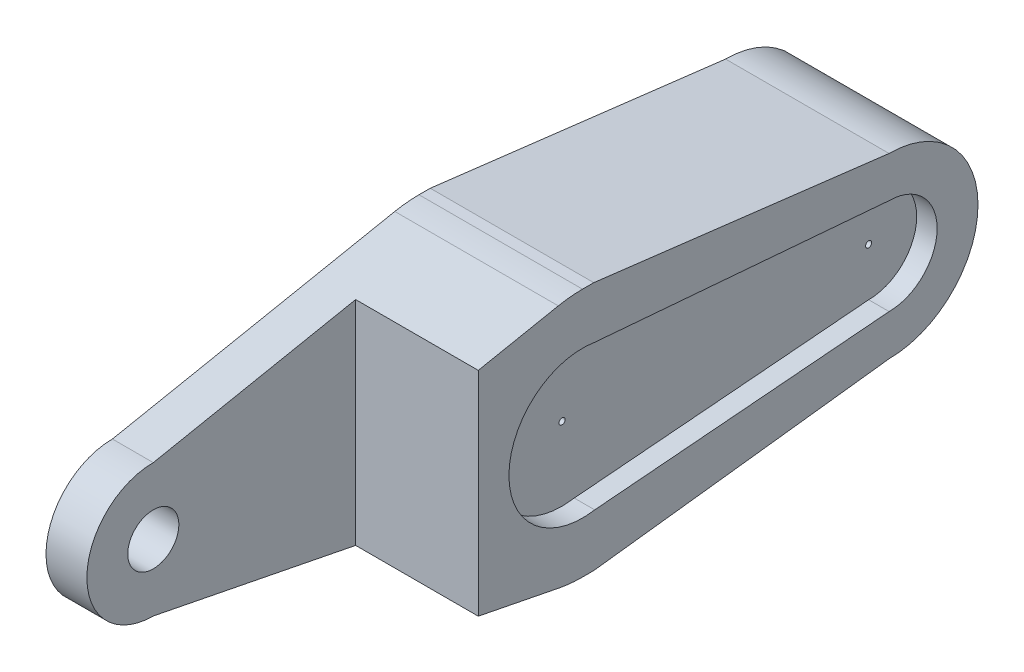
SolidWorks part; units mm, degrees
material "PLA"
ref_plane "Front Plane" through (0, 0, 0) normal (1, 0, 0) x (0, 1, 0)
ref_plane "Top Plane" through (0, 0, 0) normal (0, 0, 1) x (0, 1, 0)
ref_plane "Right Plane" through (0, 0, 0) normal (0, 1, 0) x (-1, 0, 0)
sketch "Sketch2" plane through (0, 0, 0) normal (1, 0, 0) x (0, 1, 0)
  line L0 (0, -13.9832) -> (0, -33.5576) construction
  line L1 (-6.1, -18.8) -> (6.1, -18.8)
  line L2 (-6.1, -18.8) -> (-6.1, 18.8)
  line L3 (-6.1, 18.8) -> (6.1, 18.8)
  line L4 (6.1, -18.8) -> (6.1, 18.8)
  line L5 (-6.1, -18.8) -> (6.1, 18.8) construction
  line L6 (-6.1, 18.8) -> (6.1, -18.8) construction
  line L7 (2.35, -14.45) -> (3.6, 0.55)
  line L8 (-3.6, 0.55) -> (-2.35, -14.45)
  line L9 (-6.1, 0) -> (-4.35, -14.45)
  line L10 (4.35, -14.45) -> (6.1, 0)
  line L11 (-3.25, 15.55) -> (-5.984, 1.7341)
  line L12 (5.984, 1.7341) -> (3.25, 15.55)
  arc A1 (3.5503, -0.0459) -> (-3.5503, -0.0459) centre (0, 0.55) ccw
  arc A2 (-2.35, -14.45) -> (2.35, -14.45) centre (0, -14.45) ccw
  circle A3 centre (0, 15.55) radius 1.25
  arc A4 (3.25, 15.55) -> (-3.25, 15.55) centre (0, 15.55) ccw
  arc A5 (-4.35, -14.45) -> (4.35, -14.45) centre (0, -14.45) ccw
  arc A6 (-5.984, 1.7341) -> (-6.1, 0.55) centre (0, 0.55) ccw
  arc A7 (6.1, 0.55) -> (5.984, 1.7341) centre (0, 0.55) ccw
  point P0 (0, 0)
  point P13 (6.1, -18.8)
  dimension "D1" = 7.2
  dimension "D2" = 4.7
  dimension "D4" = 2.5
  dimension "D5" = 2
  dimension "D8" = 2
  dimension "D3" = 15
  dimension "D6" = 15
  dimension "D7" = 2.5
extrude "Boss-Extrude1" add sketch "Sketch2" along normal blind 8 contours L4 A7 L12 A4 L11 A6 L2 L9 A5 L10 A3 A2 L8 A1 L7 region at (0, -2.7964, -17.2464)
extrude "Boss-Extrude2" add sketch "Sketch2<3>" along normal blind 7 contours L8 A2 L7 A1 region at (0, 0, -5.6231)
sketch "Sketch2<3>" plane through (0, 0, 0) normal (1, 0, 0) x (0, 1, 0) same geometry as "Sketch2"
sketch "Sketch3" plane through (7, 0, 0) normal (1, 0, 0) x (0, 1, 0)
  circle A0 centre (0, 0.55) radius 0.15
  arc A1 (3.6, 0.55) -> (-3.6, 0.55) centre (0, 0.55) ccw construction
  circle A2 centre (0, -14.45) radius 0.15
  arc A3 (-2.35, -14.45) -> (2.35, -14.45) centre (0, -14.45) ccw construction
  dimension "D1" = 0.3
extrude "Cut-Extrude1" cut sketch "Sketch3" against normal through all
sketch "Sketch4" plane through (8, 0, 0) normal (1, 0, 0) x (0, 1, 0)
  line L0 (5.2091, 5.65) -> (-5.2091, 5.65)
  line L1 (5.984, 1.7341) -> (3.25, 15.55) construction
  line L2 (-3.25, 15.55) -> (-5.984, 1.7341) construction
  line L3 (0, 4.15) -> (-5.8706, 4.15) construction
  line L10 (6.1, 0) -> (6.1, 0.55)
  line L11 (5.984, 1.7341) -> (3.25, 15.55)
  line L12 (-3.25, 15.55) -> (-5.984, 1.7341)
  line L13 (-6.1, 0.55) -> (-6.1, 0)
  line L14 (-6.1, 0) -> (-4.35, -14.45)
  line L15 (4.35, -14.45) -> (6.1, 0)
  line L16 (6.1, 0) -> (6.1, 0.55)
  line L17 (5.984, 1.7341) -> (3.25, 15.55)
  line L18 (-3.25, 15.55) -> (-5.984, 1.7341)
  line L19 (-6.1, 0.55) -> (-6.1, 0)
  line L20 (-6.1, 0) -> (-4.35, -14.45)
  line L21 (4.35, -14.45) -> (6.1, 0)
  arc A0 (3.6, 0.55) -> (-3.6, 0.55) centre (0, 0.55) ccw construction
  arc A5 (6.1, 0.55) -> (5.984, 1.7341) centre (0, 0.55) ccw
  arc A6 (3.25, 15.55) -> (-3.25, 15.55) centre (0, 15.55) ccw
  arc A7 (-5.984, 1.7341) -> (-6.1, 0.55) centre (0, 0.55) ccw
  arc A8 (-4.35, -14.45) -> (4.35, -14.45) centre (0, -14.45) ccw
  arc A9 (6.1, 0.55) -> (5.984, 1.7341) centre (0, 0.55) ccw
  arc A10 (3.25, 15.55) -> (-3.25, 15.55) centre (0, 15.55) ccw
  arc A11 (-5.984, 1.7341) -> (-6.1, 0.55) centre (0, 0.55) ccw
  arc A12 (-4.35, -14.45) -> (4.35, -14.45) centre (0, -14.45) ccw
  circle M13 centre (0, 15.55) radius 1.25
  line M20 (5.984, 1.7341) -> (3.25, 15.55)
  arc M21 (3.25, 15.55) -> (-3.25, 15.55) centre (0, 15.55) ccw
  line M22 (-3.25, 15.55) -> (-5.984, 1.7341)
  dimension "D1" = 1.5
  dimension "D2" = 0
extrude "Cut-Extrude2" cut sketch "Sketch4" against normal blind 6 contours L0 M20 M21 M22 M13 region at (8, 0, 11.1105)
